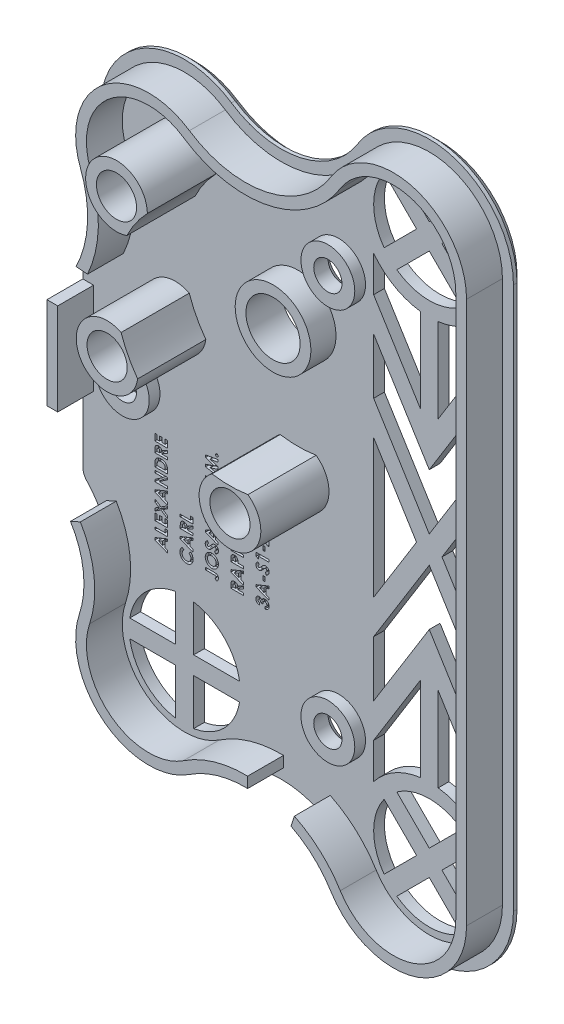
SolidWorks part; units mm, degrees
ref_plane "Plan de face" through (0, 0, 0) normal (1, 0, 0) x (0, 1, 0)
ref_plane "Plan de dessus" through (0, 0, 0) normal (0, 0, 1) x (0, 1, 0)
ref_plane "Plan de droite" through (0, 0, 0) normal (0, 1, 0) x (-1, 0, 0)
sketch "Esquisse1" plane through (0, 0, 0) normal (0, 0, 1) x (0, 1, 0)
  line L1 (-100, -60) -> (100, -60)
  line L2 (-100, -60) -> (-100, 60)
  line L3 (-100, 60) -> (100, 60)
  line L4 (100, -60) -> (100, 60)
  line L5 (-100, -60) -> (100, 60) construction
  line L6 (-100, 60) -> (100, -60) construction
  point P0 (0, 0)
  dimension "D1" = 200
  dimension "D2" = 120
extrude "Boss.-Extru.1" add sketch "Esquisse1" along normal blind 3
sketch "Esquisse3" plane through (0, 0, 0) normal (0, 0, -1) x (1, 0, 0)
  line L0 (60, -100) -> (-60, -100) construction
  line L1 (-60, -100) -> (-60, 100) construction
  circle A0 centre (-31.62, -60.23) radius 5.6
  circle A1 centre (0, 0.51) radius 5.6
  circle A2 centre (-34.24, -20.27) radius 5.6
  circle A3 centre (0, -38.09) radius 7.55
  dimension "D3" = 11.2
  dimension "D8" = 15.1
  dimension "D1" = 100.51
  dimension "D2" = 60
  dimension "D4" = 34.24
  dimension "D5" = 31.62
  dimension "D6" = 60.74
  dimension "D7" = 20.78
  dimension "D9" = 38.6
extrude "Enlèv. mat.-Extru.1" cut sketch "Esquisse3" against normal through all
sketch "Esquisse6" plane through (0, 0, 3) normal (0, 0, 1) x (1, 0, 0)
  line L0 (60, 75.09) -> (60, -76.11)
  line L1 (-60, 21.11) -> (-60, -28.89)
  line L2 (0, -0.51) -> (137.4779, -0.51) construction
  arc A0 (-18.5906, 79.7392) -> (-53.5274, 51.8373) centre (-31.62, 60.23) ccw
  arc A1 (60, 75.09) -> (16.5724, 87.4053) centre (36.54, 75.09) ccw
  arc A2 (-18.5906, 79.7392) -> (16.5724, 87.4053) centre (-4.706, 100.529) ccw
  arc A3 (-58.9343, 23.8285) -> (-60, 21.11) centre (-56, 21.11) ccw
  arc A4 (-60, -28.89) -> (-58.8853, -31.6603) centre (-56, -28.89) ccw
  arc A5 (-58.9343, 23.8285) -> (-53.5274, 51.8373) centre (-78.7405, 42.1782) ccw
  arc A6 (-53.88, -53.8431) -> (-58.8853, -31.6603) centre (-74.7548, -46.8972) ccw
  arc A7 (-18.5906, -80.7592) -> (16.5724, -88.4253) centre (-4.706, -101.549) cw
  arc A8 (60, -76.11) -> (16.5724, -88.4253) centre (36.54, -76.11) cw
  arc A9 (-18.5906, -80.7592) -> (-53.88, -53.8431) centre (-31.62, -61.25) cw
  line M4 (60, 100) -> (-60, 100)
  line M5 (-60, 100) -> (-60, -100)
  line M6 (-60, -100) -> (60, -100)
  line M7 (60, -100) -> (60, 100)
  dimension "D1" = 46.92
  dimension "D4" = 25
  dimension "D8" = 8
  dimension "D9" = 27
  dimension "D10" = 22
  dimension "D2" = 68.16
  dimension "D3" = 14.86
  dimension "D5" = 50
  dimension "D6" = 24.38
  dimension "D7" = 39.12
extrude "Enlèv. mat.-Extru.3" cut sketch "Esquisse6" against normal through all contours L2 L0 A8 A7 A9 A6 A4 M5 M6 M7 | L0 L2 A3 A5 A0 A2 A1 M7 M4 M5 region at (-20.1198, 84.1249, 3) region at (-20.2617, -85.7725, 3)
sketch "Esquisse4" plane through (0, 0, 0) normal (0, 0, -1) x (1, 0, 0)
  line L0 (0, 0.51) -> (-83.2465, 0.51) construction
  circle A0 centre (11.28, -54.49) radius 3.935
  circle A1 centre (-46, 0.51) radius 3.935
  circle A2 centre (0, 0.51) radius 5.6 construction
  circle A3 centre (11.28, 55.51) radius 3.935
  dimension "D1" = 7.87
  dimension "D2" = 11.28
  dimension "D3" = 55
  dimension "D4" = 46
extrude "Enlèv. mat.-Extru.2" cut sketch "Esquisse4" against normal blind 10
sketch "Esquisse5" plane through (0, 0, 3) normal (0, 0, 1) x (1, 0, 0)
  circle A1 centre (11.28, -55.51) radius 3.935 construction
  circle A2 centre (-46, -0.51) radius 7.5
  circle A3 centre (11.28, 54.49) radius 7.5
  circle A4 centre (11.28, -55.51) radius 7.5
  circle A6 centre (-46, -0.51) radius 3.935 construction
  circle A7 centre (11.28, 54.49) radius 3.935 construction
  circle M2 centre (11.28, 54.49) radius 3.935
  circle M3 centre (11.28, -55.51) radius 3.935
  circle M4 centre (-46, -0.51) radius 3.935
  dimension "D1" = 15
extrude "Boss.-Extru.3" add sketch "Esquisse5" along normal blind 3 contours A2 M4 | A4 M3 | A3 M2 region at (-53.2879, -0.51, 3) region at (3.9921, 54.49, 3) region at (3.9921, -55.51, 3)
sketch "Esquisse7" plane through (0, 0, 3) normal (0, 0, 1) x (1, 0, 0)
  line L0 (-60, 21.11) -> (-60, -28.89) construction
  line L1 (-60, -9.0844) -> (-57, -9.0844)
  line L2 (-60, -9.0844) -> (-60, 16.5385)
  line L3 (-60, 16.5385) -> (-57, 16.5385)
  line L4 (-57, -9.0844) -> (-57, 16.5385)
  dimension "D1" = 3
extrude "Boss.-Extru.4" add sketch "Esquisse7" along normal blind 10
sketch "Esquisse8" plane through (0, 0, 3) normal (0, 0, 1) x (1, 0, 0)
  circle A3 centre (0, 38.09) radius 10.55
  circle A4 centre (0, 38.09) radius 10.55
  circle M5 centre (0, 38.09) radius 7.55
  dimension "D1" = 3
extrude "Boss.-Extru.5" add sketch "Esquisse8" along normal blind 7 contours A4 M5 region at (-10.2516, 38.09, 3)
sketch "Esquisse9" plane through (0, 0, 0) normal (0, 0, -1) x (1, 0, 0)
  line L0 (36.54, -75.09) -> (36.54, 76.11) construction
  line L1 (21.04, -75.09) -> (21.04, 76.11)
  line L2 (52.04, -75.09) -> (52.04, 76.11)
  line L3 (36.54, 76.11) -> (-19.7348, 76.11) construction
  line L4 (36.54, 0.51) -> (-0.0036, 0.51) construction
  line L5 (21.04, -53.2578) -> (36.54, -28.2578)
  line L6 (36.54, -28.2578) -> (52.04, -53.2578)
  line L7 (39.04, -55.7509) -> (39.04, -32.2901)
  line L8 (36.54, -75.09) -> (36.54, 76.11) construction
  line L9 (21.04, -43.7691) -> (36.54, -18.7691)
  line L10 (36.54, -18.7691) -> (52.04, -43.7691)
  line L11 (36.54, -18.7691) -> (56.2895, -50.6231) construction
  line L12 (16.7905, -50.6231) -> (36.54, -18.7691) construction
  line L13 (36.54, -75.09) -> (36.54, -123.3004) construction
  line L14 (34.04, -55.7509) -> (34.04, -32.2901)
  line L15 (36.54, -3.2578) -> (52.04, -28.2578)
  line L16 (36.54, 6.2309) -> (52.04, -18.7691)
  line L17 (21.04, -28.2578) -> (36.54, -3.2578)
  line L18 (21.04, -18.7691) -> (36.54, 6.2309)
  line L19 (21.04, 19.7891) -> (36.54, -5.2109)
  line L20 (36.54, 4.2778) -> (52.04, 29.2778)
  line L21 (36.54, -5.2109) -> (52.04, 19.7891)
  line L22 (21.04, 29.2778) -> (36.54, 4.2778)
  line L23 (21.04, 54.2778) -> (36.54, 29.2778)
  line L24 (34.04, 56.7709) -> (34.04, 33.3101)
  line L25 (39.04, 56.7709) -> (39.04, 33.3101)
  line L26 (36.54, 29.2778) -> (52.04, 54.2778)
  line L27 (36.54, 19.7891) -> (52.04, 44.7891)
  line L28 (21.04, 44.7891) -> (36.54, 19.7891)
  line L29 (36.54, 76.11) -> (25.5798, 87.0702) construction
  line L30 (27.4911, 88.6944) -> (49.1244, 67.0611)
  line L31 (23.9556, 85.1589) -> (45.5889, 63.5256)
  line L32 (45.5889, 88.6944) -> (23.9556, 67.0611)
  line L33 (49.1244, 85.1589) -> (27.4911, 63.5256)
  line L34 (45.5889, -87.6744) -> (23.9556, -66.0411)
  line L35 (49.1244, -84.1389) -> (27.4911, -62.5056)
  line L36 (27.4911, -87.6744) -> (49.1244, -66.0411)
  line L37 (23.9556, -84.1389) -> (45.5889, -62.5056)
  line L38 (-31.62, 61.25) -> (-83.0942, 61.25) construction
  line L39 (-46.9171, 63.75) -> (-16.3229, 63.75)
  line L40 (-46.9171, 58.75) -> (-16.3229, 58.75)
  line L41 (-31.62, 61.25) -> (-75.4203, 105.0503) construction
  line L42 (-29.12, 76.5471) -> (-29.12, 45.9529)
  line L43 (-34.12, 76.5471) -> (-34.12, 45.9529)
  circle A2 centre (-31.62, 61.25) radius 15.5
  arc A3 (-18.5906, 80.7592) -> (-53.88, 53.8431) centre (-31.62, 61.25) ccw construction
  circle A5 centre (36.54, -75.09) radius 15.5
  arc A6 (52.04, -63.2578) -> (21.04, -63.2578) centre (36.54, -75.09) ccw
  circle A7 centre (36.54, -75.09) radius 19.5 construction
  circle A8 centre (36.54, 76.11) radius 15.5
  arc A9 (52.04, 64.2778) -> (21.04, 64.2778) centre (36.54, 76.11) cw
  arc A10 (16.5724, -87.4053) -> (60, -75.09) centre (36.54, -75.09) ccw construction
  point P2 (36.54, 0.51)
  dimension "D2" = 4
  dimension "D10" = 31
  dimension "D1" = 151.2
  dimension "D3" = 31
  dimension "D4" = 10
  dimension "D5" = 25
  dimension "D6" = 5
  dimension "D9" = 25
  dimension "D11" = 45
  dimension "D12" = 2.5
  dimension "D13" = 2.5
  dimension "D14" = 45
  dimension "D7" = 5
  dimension "D8" = 2
extrude "Enlèv. mat.-Extru.4" cut sketch "Esquisse9" against normal blind 19 contours A6 L14 L5 L1 | L2 A9 L25 L26 | L24 A9 L1 L23 | L28 L1 L22 L18 L16 L20 L2 L27 | L21 L16 L2 | L18 L22 L20 L16 | L19 L1 L18 | L21 L19 L17 L1 L9 L10 L2 L15 | L19 L21 L15 L17 | L35 A5 L36 | A5 L37 L34 | L36 A5 L34 | L37 A5 L35 | A8 L30 L32 | A8 L31 L33 | A8 L32 L31 | A8 L33 L30 | L39 A2 L42 | L42 A2 L40 | L40 A2 L43 | L43 A2 L39 | A6 L2 L6 L7 region at (25.6941, 75.09, 0) region at (28.4995, 49.5256, 0) region at (36.54, 64.2441, 0) region at (36.54, 85.9359, 0) region at (21.5424, 36.0135, 0) region at (44.5805, 49.5256, 0) region at (47.3859, 75.09, 0) region at (25.0243, -0.51, 0) region at (36.54, 4.2344, 0) region at (21.5424, -37.0335, 0) region at (36.54, -5.2544, 0) region at (48.0557, -0.51, 0) region at (28.4995, -50.5456, 0) region at (25.6941, -76.11, 0) region at (44.5805, -50.5456, 0) region at (36.54, -86.9559, 0) region at (36.54, -65.2641, 0) region at (47.3859, -76.11, 0) region at (-39.2892, -68.9192, 0) region at (-39.2892, -53.5808, 0) region at (-23.9508, -68.9192, 0) region at (-23.9508, -53.5808, 0)
sketch "Esquisse10" plane through (0, 0, 3) normal (0, 0, 1) x (1, 0, 0)
  circle A1 centre (-31.62, 60.23) radius 5.6 construction
  circle A2 centre (-31.62, 60.23) radius 8.6
  circle A3 centre (-31.62, 60.23) radius 8.6
  circle A4 centre (-31.62, 60.23) radius 5.6
  circle A6 centre (-34.24, 20.27) radius 5.6 construction
  circle A7 centre (-34.24, 20.27) radius 8.6
  circle A8 centre (-34.24, 20.27) radius 8.6
  circle A9 centre (-34.24, 20.27) radius 5.6
  circle A11 centre (0, -0.51) radius 5.6 construction
  circle A12 centre (0, -0.51) radius 8.6
  circle A13 centre (0, -0.51) radius 8.6
  circle A14 centre (0, -0.51) radius 5.6
  dimension "D1" = 3
  dimension "D2" = 3
  dimension "D3" = 3
extrude "Boss.-Extru.6" add sketch "Esquisse10" along normal blind 19
sketch "Esquisse11" plane through (0, 0, 3) normal (0, 0, 1) x (1, 0, 0)
  line L0 (-51.9161, 28.5894) -> (-48.7142, 28.3201)
  line L1 (-53.4473, -33.6874) -> (-50.6951, -32.4383)
  line L6 (53.93, -76.11) -> (53.93, 75.09)
  line L7 (-52.0824, 22.6085) -> (-52.0824, 22.6085)
  line L8 (-52.0824, 22.6085) -> (-50.93, 22.6085)
  line L9 (-50.93, 22.6085) -> (-50.93, -15.1544)
  line L10 (-50.93, -15.1544) -> (-53.93, -15.1544)
  line L11 (-53.93, -15.1544) -> (-53.93, -28.0755)
  line L12 (-53.93, -12.1544) -> (-56.93, -12.1544)
  line L13 (-56.93, -12.1544) -> (-56.93, -28.89)
  line L14 (56.93, -76.11) -> (56.93, 75.09)
  line L15 (-56.93, 21.11) -> (-56.93, 19.6085)
  line L16 (-56.93, 19.6085) -> (-53.93, 19.6085)
  line L17 (-53.93, 19.6085) -> (-53.93, -12.1544)
  line L18 (-53.93, -12.1544) -> (-56.93, -12.1544)
  line L19 (-56.93, -12.1544) -> (-56.93, -28.89)
  line L20 (56.93, -76.11) -> (56.93, 75.09)
  line L21 (-56.93, 21.11) -> (-56.93, 19.6085)
  line L22 (-56.93, 19.6085) -> (-53.93, 19.6085)
  line L23 (-53.93, 19.6085) -> (-53.93, -12.1544)
  line L26 (-4.0698, -70.4855) -> (-4.0698, -73.4862)
  line L27 (8.0012, -76.5199) -> (8.9444, -73.6382)
  arc A10 (-48.1205, -55.7596) -> (-21.9618, -75.7114) centre (-31.62, -61.25) ccw
  arc A11 (21.7388, -85.2388) -> (-21.9618, -75.7114) centre (-4.706, -101.549) ccw
  arc A12 (21.7388, -85.2388) -> (53.93, -76.11) centre (36.54, -76.11) ccw
  arc A13 (53.93, 75.09) -> (21.7388, 84.2188) centre (36.54, 75.09) ccw
  arc A14 (-21.9618, 74.6914) -> (21.7388, 84.2188) centre (-4.706, 100.529) ccw
  arc A15 (-21.9618, 74.6914) -> (-47.8591, 54.0088) centre (-31.62, 60.23) ccw
  arc A16 (-52.0824, 22.6085) -> (-47.8591, 54.0088) centre (-78.7405, 42.1782) ccw
  arc A17 (-52.0824, 22.6085) -> (-52.0824, 22.6085) centre (-52.0824, 22.6085) ccw
  arc A18 (-53.93, -28.0755) -> (-53.93, -28.0755) centre (-53.93, -28.0755) ccw
  arc A19 (-48.1205, -55.7596) -> (-53.93, -28.0755) centre (-74.7548, -46.8972) ccw
  arc A20 (-56.93, -28.89) -> (-56.6708, -29.5341) centre (-56, -28.89) ccw
  arc A21 (-50.9671, -54.8124) -> (-56.6708, -29.5341) centre (-74.7548, -46.8972) ccw
  arc A22 (-50.9671, -54.8124) -> (-20.2957, -78.2062) centre (-31.62, -61.25) ccw
  arc A23 (19.1854, -86.8137) -> (-20.2957, -78.2062) centre (-4.706, -101.549) ccw
  arc A24 (19.1854, -86.8137) -> (56.93, -76.11) centre (36.54, -76.11) ccw
  arc A25 (56.93, 75.09) -> (19.1854, 85.7937) centre (36.54, 75.09) ccw
  arc A26 (-20.2957, 77.1862) -> (19.1854, 85.7937) centre (-4.706, 100.529) ccw
  arc A27 (-20.2957, 77.1862) -> (-50.6606, 52.9356) centre (-31.62, 60.23) ccw
  arc A28 (-56.6822, 21.742) -> (-50.6606, 52.9356) centre (-78.7405, 42.1782) ccw
  arc A29 (-56.6822, 21.742) -> (-56.93, 21.11) centre (-56, 21.11) ccw
  arc A30 (-56.93, -28.89) -> (-56.6708, -29.5341) centre (-56, -28.89) ccw
  arc A31 (-50.9671, -54.8124) -> (-56.6708, -29.5341) centre (-74.7548, -46.8972) ccw
  arc A32 (-50.9671, -54.8124) -> (-20.2957, -78.2062) centre (-31.62, -61.25) ccw
  arc A33 (19.1854, -86.8137) -> (-20.2957, -78.2062) centre (-4.706, -101.549) ccw
  arc A34 (19.1854, -86.8137) -> (56.93, -76.11) centre (36.54, -76.11) ccw
  arc A35 (56.93, 75.09) -> (19.1854, 85.7937) centre (36.54, 75.09) ccw
  arc A36 (-20.2957, 77.1862) -> (19.1854, 85.7937) centre (-4.706, 100.529) ccw
  arc A37 (-20.2957, 77.1862) -> (-50.6606, 52.9356) centre (-31.62, 60.23) ccw
  arc A38 (-56.6822, 21.742) -> (-50.6606, 52.9356) centre (-78.7405, 42.1782) ccw
  arc A39 (-56.6822, 21.742) -> (-56.93, 21.11) centre (-56, 21.11) ccw
  dimension "D1" = 3.07
  dimension "D2" = 3
extrude "Boss.-Extru.7" add sketch "Esquisse11" along normal blind 10 contours A38 A16 A15 A14 A13 L6 A12 A11 A10 A19 A30 A31 A32 A33 A34 L20 A35 A36 A37 | A33 L26 A11 A10 A19 A30 A31 A32 region at (-46.506, 40.5158, 3) region at (-47.5471, -43.8935, 3)
sketch "Esquisse12" plane through (0, 0, 3) normal (0, 0, 1) x (1, 0, 0)
  line L0 (-36.4227, -37.8868) -> (-36.4227, 24.1469) construction
  text T0 "<b>ALEXANDRE</b>\r\n<b>CARL</b>\r\n<b>JOSAPHAT M.</b>\r\n<b>RAPHAEL</b>\r\n<b>3A-S1-2025</b>"
extrude "Enlèv. mat.-Extru.5" cut sketch "Esquisse12" against normal blind 1
chamfer "Chanfrein1" distance 2 angle 45 12 edges at (-53.2943, -42.0549, 0) (-59.7109, -30.3831, 0) (-45.8474, -79.9035, 0) (-60, -3.89, 0) (0.6193, -77.1227, 0) (-59.724, 22.57, 0) (42.9404, -98.68, 0) (-52.23, 37.0606, 0) (60, -0.51, 0) (-46.2601, 78.5613, 0) (42.9404, 97.66, 0) (0.6193, 76.1027, 0)
sketch "Esquisse13" plane through (0, 0, 22) normal (0, 0, 1) x (1, 0, 0)
  line L0 (0, 38.09) -> (17.5063, 11.3033)
  line L1 (0, 38.09) -> (-20.2918, 62.8336)
  arc A0 (-20.2918, 62.8336) -> (17.5063, 11.3033) centre (0, 38.09) ccw
  arc A1 (-14.1459, 55.3394) -> (12.2041, 19.4162) centre (0, 38.09) ccw
  circle M2 centre (-34.24, 20.27) radius 8.6
  dimension "D1" = 64
  dimension "D2" = 22.3081
extrude "Enlèv. mat.-Extru.6" cut sketch "Esquisse13" against normal up to surface (19 mm away) contours A1 L1 A0 L0 M2 | A0 M2 region at (14.2248, 14.9478, 22) region at (-27.6001, 23.7257, 22) up to face at (-16.7602, -36.4805, 3)
chamfer "Chanfrein2" distance 2 angle 45 3 edges at (7.345, 54.49, 0) (15.215, -55.51, 0) (-49.935, -0.51, 0)
